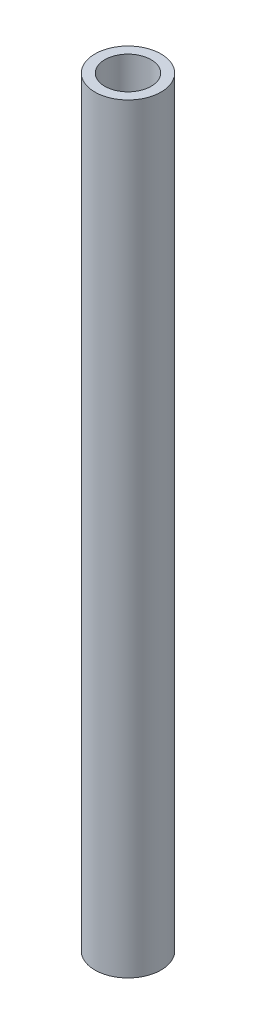
SolidWorks part; units mm, degrees
material "PLA"
ref_plane "Front" through (0, 0, 0) normal (0, 0, 1) x (1, 0, 0)
ref_plane "Top" through (0, 0, 0) normal (0, 1, 0) x (1, 0, 0)
ref_plane "Right" through (0, 0, 0) normal (1, 0, 0) x (0, 0, -1)
sketch "Sketch1" plane through (0, 0, 0) normal (0, 1, 0) x (1, 0, 0)
  circle A0 centre (0, 0) radius 6.35
  dimension "D1" = 12.7
extrude "Boss-Extrude1" add sketch "Sketch1" along normal blind 146.05
sketch "Sketch2" plane through (0, 146.05, 0) normal (0, 1, 0) x (1, 0, 0)
  circle A0 centre (0, 0) radius 4.445
  dimension "D1" = 8.89
extrude "Cut-Extrude1" cut sketch "Sketch2" against normal blind 146.05 contours A0
